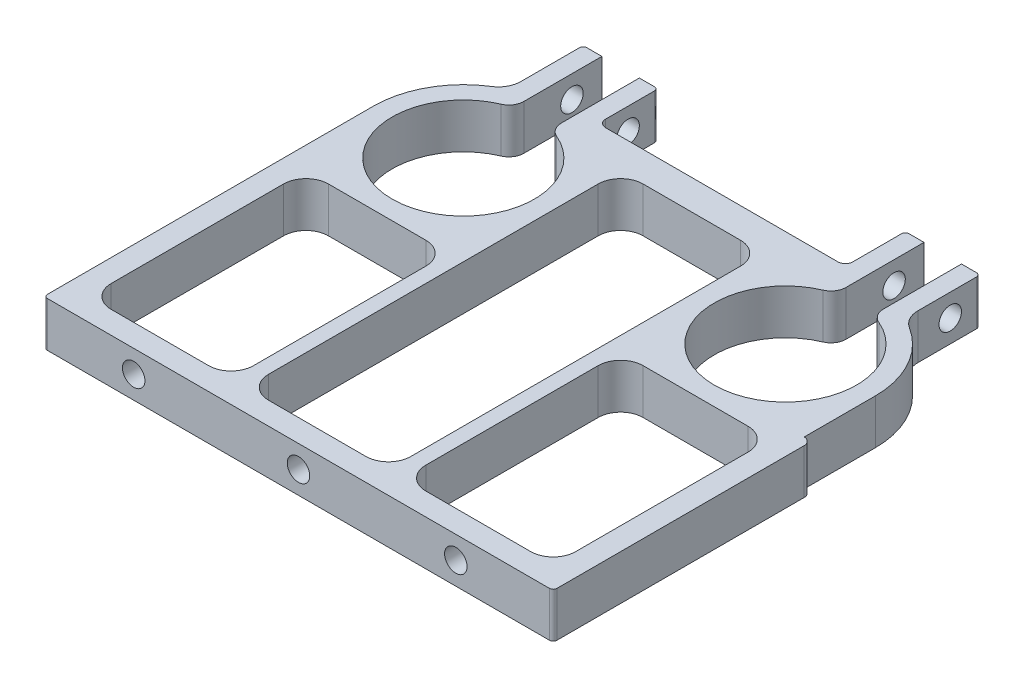
SolidWorks part; units mm, degrees
ref_plane "前视基准面" through (0, 0, 0) normal (0, 0, 1) x (1, 0, 0)
ref_plane "上视基准面" through (0, 0, 0) normal (0, 1, 0) x (1, 0, 0)
ref_plane "右视基准面" through (0, 0, 0) normal (1, 0, 0) x (0, 0, -1)
sketch "草图1" plane through (0, 0, 0) normal (0, 1, 0) x (1, 0, 0)
  line L0 (22, -25) -> (22, -54)
  line L1 (17, 0) -> (50, 0)
  line L2 (0, -13) -> (0, -57)
  line L3 (0, -57) -> (68, -57)
  line L4 (68, -22.5) -> (68, -57)
  line L5 (24, -25) -> (24, -54)
  line L6 (43, -25) -> (43, -54)
  line L7 (45, -25) -> (45, -54)
  line L8 (24, -25) -> (24, -4)
  line L9 (3, -25) -> (22, -25)
  line L10 (3, -25) -> (3, -54)
  line L11 (3, -54) -> (22, -54)
  line L12 (65, -25) -> (65, -54)
  line L13 (24, -4) -> (43, -4)
  line L14 (43, -4) -> (43, -25)
  line L15 (24, -54) -> (43, -54)
  line L16 (45, -25) -> (65, -25)
  line L17 (45, -54) -> (65, -54)
  line L18 (12, -13) -> (55, -13) construction
  line L19 (12, -13) -> (12, 4.4967) construction
  line L20 (7, -2.0913) -> (7, 8)
  line L21 (17, 0) -> (17, 8)
  line L22 (9.5, -3.8348) -> (9.5, 8)
  line L23 (14.5, 8) -> (17, 8)
  line L24 (14.5, -3.8348) -> (14.5, 8)
  line L25 (33.5, -12) -> (33.5, 8) construction
  line L26 (50, 0) -> (50, 8)
  line L27 (7, 8) -> (9.5, 8)
  line L28 (52.5, 8) -> (50, 8)
  line L29 (52.5, -3.8348) -> (52.5, 8)
  line L30 (57.5, -3.8348) -> (57.5, 8)
  line L31 (60, 8) -> (57.5, 8)
  line L32 (60, -2.0913) -> (60, 8)
  line L33 (67, -13) -> (67, -22.5)
  line L34 (67, -22.5) -> (68, -22.5)
  arc A0 (9.5, -3.8348) -> (14.5, -3.8348) centre (12, -13) ccw
  arc A1 (52.5, -3.8348) -> (57.5, -3.8348) centre (55, -13) ccw
  arc A2 (60, -2.0913) -> (67, -13) centre (55, -13) cw
  arc A4 (7, -2.0913) -> (0, -13) centre (12, -13) ccw
  point P11 (0, 0)
  dimension "D4" = 19
  dimension "D7" = 5
  dimension "D1" = 57
  dimension "D2" = 68
  dimension "D5" = 43
  dimension "D6" = 12
  dimension "D9" = 44
  dimension "D10" = 44
  dimension "D11" = 3
  dimension "D12" = 3
  dimension "D13" = 3
  dimension "D14" = 29
  dimension "D15" = 12
  dimension "D16" = 2
  dimension "D17" = 12
  dimension "D18" = 2
  dimension "D19" = 4
  dimension "D20" = 10
  dimension "D21" = 9.5
  dimension "D22" = 8
  dimension "D23" = 1
extrude "凸台-拉伸1" add sketch "草图1" along normal blind 6
sketch "草图3" plane through (0, 0, 57) normal (0, 0, 1) x (1, 0, 0)
  line L0 (0, 3) -> (81.2777, 3) construction
  line L1 (0, 6) -> (0, 0) construction
  circle A0 centre (12, 3) radius 1.5
  circle A1 centre (34, 3) radius 1.5
  circle A2 centre (55, 3) radius 1.5
  dimension "D1" = 3
  dimension "D2" = 3
  dimension "D3" = 3
  dimension "D4" = 12
  dimension "D5" = 22
  dimension "D6" = 21
extrude "切除-拉伸1" cut sketch "草图3" against normal blind 10
fillet "圆角1" radius 3 12 edges at (45, 3, 54) (24, 3, 54) (45, 3, 25) (24, 3, 4) (43, 3, 4) (65, 3, 25) (22, 3, 25) (65, 3, 54) (43, 3, 54) (22, 3, 54) (3, 3, 25) (3, 3, 54)
fillet "圆角2" radius 1 3 edges at (50, 3, 0) (17, 3, 0) (68, 3, 22.5)
sketch "草图4" plane through (7, 0, 0) normal (-1, 0, 0) x (0, 0, 1)
  line L0 (-8, 6) -> (2.0913, 6) construction
  line L1 (-8, 6) -> (-8, 0) construction
  circle A0 centre (-4, 3) radius 1.5
  dimension "D1" = 3
  dimension "D2" = 3
  dimension "D3" = 4
extrude "切除-拉伸2" cut sketch "草图4" against normal blind 72
fillet "圆角3" radius 0.5 2 edges at (68, 3, 57) (0, 3, 57)
fillet "圆角4" radius 0.5 4 edges at (60, 3, -8) (50, 3, -8) (17, 3, -8) (7, 3, -8)
fillet "圆角5" radius 3 2 edges at (7, 3, 2.0913) (60, 3, 2.0913)
fillet "圆角6" radius 2 4 edges at (52.5, 3, 3.8348) (57.5, 3, 3.8348) (14.5, 3, 3.8348) (9.5, 3, 3.8348)
